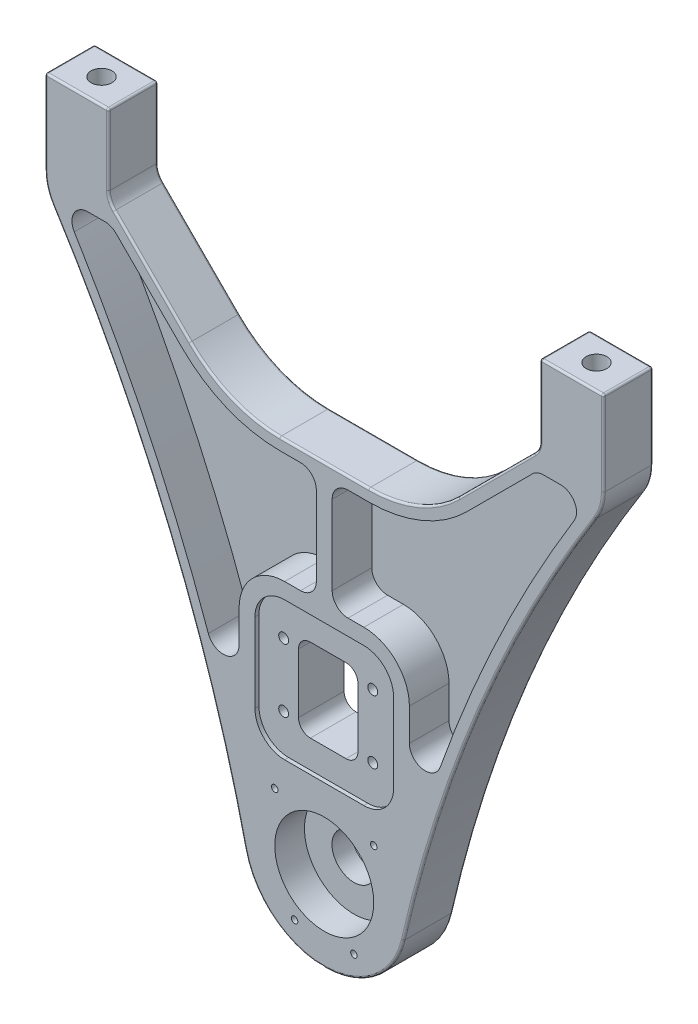
SolidWorks part; units mm, degrees
other "DetailItem2"
other "DetailItem3"
ref_plane "Front Plane" through (0, 0, 0) normal (0, 0, 1) x (1, 0, 0)
ref_plane "Top Plane" through (0, 0, 0) normal (0, 1, 0) x (1, 0, 0)
ref_plane "Right Plane" through (0, 0, 0) normal (1, 0, 0) x (0, 0, -1)
sketch "Sketch1" plane through (0, 0, 0) normal (0, 0, 1) x (1, 0, 0)
  line L0 (0, 0) -> (0, 280) construction
  line L1 (0, 280) -> (125, 280) construction
  line L2 (109, 280) -> (141, 280)
  line L3 (141, 280) -> (141, 237.3088)
  line L4 (109, 280) -> (109, 244.1421)
  line L5 (106.0711, 237.0711) -> (67.7452, 198.7452)
  line L6 (-22.4903, 180) -> (22.4903, 180)
  line L7 (0, 0) -> (0, -22.225) construction
  line L8 (-141, 280) -> (-141, 237.3088)
  line L9 (-109, 280) -> (-141, 280)
  line L10 (-109, 280) -> (-109, 244.1421)
  line L11 (-106.0711, 237.0711) -> (-67.7452, 198.7452)
  arc A0 (-39.9598, -9.1768) -> (39.9598, -9.1768) centre (0, 0) ccw
  circle A1 centre (0, 0) radius 22.5 construction
  arc A2 (137.1268, 223.9425) -> (39.9598, -9.1768) centre (770.9319, -177.0452) ccw
  arc A3 (67.7452, 198.7452) -> (22.4903, 180) centre (22.4903, 244) cw
  arc A4 (141, 237.3088) -> (137.1268, 223.9425) centre (116, 237.3088) cw
  arc A5 (109, 244.1421) -> (106.0711, 237.0711) centre (99, 244.1421) cw
  arc A6 (-137.1268, 223.9425) -> (-39.9598, -9.1768) centre (-770.9319, -177.0452) cw
  arc A7 (-141, 237.3088) -> (-137.1268, 223.9425) centre (-116, 237.3088) ccw
  arc A8 (-109, 244.1421) -> (-106.0711, 237.0711) centre (-99, 244.1421) ccw
  arc A9 (-67.7452, 198.7452) -> (-22.4903, 180) centre (-22.4903, 244) ccw
  circle A10 centre (0, 0) radius 10 construction
  point P24 (141, 230)
  point P27 (109, 240)
  point P35 (0, 180)
  dimension "D1" = 82
  dimension "D2" = 45
  dimension "D8" = 750
  dimension "D9" = 40
  dimension "D10" = 25
  dimension "D11" = 10
  dimension "D12" = 64
  dimension "D15" = 20
  dimension "D3" = 280
  dimension "D4" = 125
  dimension "D5" = 16
  dimension "D6" = 16
  dimension "D7" = 50
  dimension "D13" = 100
  dimension "D14" = 45
extrude "Boss-Extrude1" add sketch "Sketch1" along normal blind 25
sketch "Sketch2" plane through (0, 0, 25) normal (0, 0, 1) x (1, 0, 0)
  circle A0 centre (0, 0) radius 25
  dimension "D1" = 50
extrude "Cut-Extrude1" cut sketch "Sketch2" against normal blind 15
sketch "Sketch4" plane through (0, 0, 25) normal (0, 0, 1) x (1, 0, 0)
  line L9 (0, 0) -> (0, 180) construction
  line L10 (22.4903, 180) -> (-22.4903, 180) construction
  line L12 (-20, 40) -> (20, 40)
  line L13 (-35, 55) -> (-35, 95)
  line L14 (-20, 110) -> (20, 110)
  line L15 (35, 55) -> (35, 95)
  line L16 (-35, 40) -> (35, 110) construction
  line L17 (-35, 110) -> (35, 40) construction
  arc A7 (20, 40) -> (35, 55) centre (20, 55) ccw
  arc A8 (-20, 40) -> (-35, 55) centre (-20, 55) cw
  arc A9 (-35, 95) -> (-20, 110) centre (-20, 95) cw
  arc A10 (20, 110) -> (35, 95) centre (20, 95) cw
  point P8 (0, 75)
  dimension "D4" = 15
  dimension "D1" = 70
  dimension "D2" = 70
  dimension "D3" = 70
extrude "Cut-Extrude3" cut sketch "Sketch4" against normal blind 2
sketch "Sketch5" plane through (0, 0, 25) normal (0, 0, 1) x (1, 0, 0)
  line L0 (22.4903, 174) -> (12, 174)
  line L1 (141, 280) -> (109, 280) construction
  line L2 (106.0711, 237.0711) -> (67.7452, 198.7452) construction
  line L3 (22.4903, 180) -> (-22.4903, 180) construction
  line L4 (4, 166) -> (4, 126)
  line L5 (-43, 95) -> (-43, 78.6774)
  line L6 (-119.4268, 230) -> (-110.799, 230)
  line L7 (43, 95) -> (43, 78.6774)
  line L8 (0, 0) -> (0, 188.5352) construction
  line L9 (-105.1421, 227.6569) -> (-71.9878, 194.5025)
  line L10 (105.1421, 227.6569) -> (71.9878, 194.5025)
  line L11 (119.4268, 230) -> (110.799, 230)
  line L12 (20, 118) -> (-20, 118)
  line L13 (20, 118) -> (12, 118)
  line L14 (-22.4903, 174) -> (-12, 174)
  line L15 (-4, 166) -> (-4, 126)
  line L16 (-20, 118) -> (-12, 118)
  arc A0 (137.1268, 223.9425) -> (39.9598, -9.1768) centre (770.9319, -177.0452) ccw construction
  arc A1 (22.4903, 180) -> (67.7452, 198.7452) centre (22.4903, 244) ccw construction
  arc A2 (4, 126) -> (12, 118) centre (12, 126) ccw
  arc A3 (12, 174) -> (4, 166) centre (12, 166) ccw
  arc A4 (-43, 78.6774) -> (-58.5386, 75.9997) centre (-51, 78.6774) cw
  arc A5 (-58.5386, 75.9997) -> (-126.2488, 217.8215) centre (-770.9319, -177.0452) ccw
  arc A6 (-126.2488, 217.8215) -> (-119.4268, 230) centre (-119.4268, 222) cw
  arc A7 (43, 78.6774) -> (58.5386, 75.9997) centre (51, 78.6774) ccw
  arc A8 (-105.1421, 227.6569) -> (-110.799, 230) centre (-110.799, 222) ccw
  arc A9 (-71.9878, 194.5025) -> (-22.4903, 174) centre (-22.4903, 244) ccw
  arc A10 (-12, 174) -> (-4, 166) centre (-12, 166) cw
  arc A11 (-4, 126) -> (-12, 118) centre (-12, 126) cw
  arc A12 (-43, 95) -> (-20, 118) centre (-20, 95) cw
  arc A13 (71.9878, 194.5025) -> (22.4903, 174) centre (22.4903, 244) cw
  arc A14 (105.1421, 227.6569) -> (110.799, 230) centre (110.799, 222) cw
  arc A15 (126.2488, 217.8215) -> (119.4268, 230) centre (119.4268, 222) ccw
  arc A16 (58.5386, 75.9997) -> (126.2488, 217.8215) centre (770.9319, -177.0452) cw
  arc A17 (43, 95) -> (20, 118) centre (20, 95) ccw
  arc A18 (43, 95) -> (20, 118) centre (20, 95) ccw
  dimension "D4" = 6
  dimension "D5" = 6
  dimension "D6" = 8
  dimension "D8" = 8
  dimension "D1" = 6
  dimension "D3" = 6
  dimension "D9" = 8
  dimension "D10" = 8
  dimension "D7" = 4
  dimension "D2" = 50
extrude "Cut-Extrude4" cut sketch "Sketch5" against normal blind 20
fillet "Fillet1" radius 1 40 edges at (-140.0122, 230.3507, 25) (-141, 258.6544, 25) (-125, 280, 25) (-109, 262.0711, 25) (-108.2388, 240.3153, 25) (-86.9081, 217.9081, 25) (-46.9821, 184.8717, 25) (0, 180, 25) (46.9821, 184.8717, 25) (86.9081, 217.9081, 25) (108.2388, 240.3153, 25) (109, 262.0711, 25) (125, 280, 25) (141, 258.6544, 25) (140.0122, 230.3507, 25) (78.66, 111.5023, 25) (0, -41, 25) (-78.66, 111.5023, 25) (0, -41, 0) (78.66, 111.5023, 0) (140.0122, 230.3507, 0) (141, 258.6544, 0) (125, 280, 0) (109, 262.0711, 0) (108.2388, 240.3153, 0) (86.9081, 217.9081, 0) (46.9821, 184.8717, 0) (0, 180, 0) (-46.9821, 184.8717, 0) (-86.9081, 217.9081, 0) (-108.2388, 240.3153, 0) (-109, 262.0711, 0) (-125, 280, 0) (-141, 258.6544, 0) (-140.0122, 230.3507, 0) (-78.66, 111.5023, 0) (141, 280, 12.5) (109, 280, 12.5) (-109, 280, 12.5) (-141, 280, 12.5)
sketch "Sketch3" plane through (0, 0, 10) normal (0, 0, 1) x (1, 0, 0)
  circle A0 centre (0, 0) radius 11.1125
  dimension "D1" = 22.225
extrude "Cut-Extrude2" cut sketch "Sketch3" against normal blind 19.05
sketch "Sketch10" plane through (0, 0, 23) normal (0, 0, 1) x (1, 0, 0)
  line L4 (35, 75) -> (-35, 75) construction
  line L5 (35, 55) -> (35, 95) construction
  line L6 (-35, 95) -> (-35, 55) construction
  line L7 (0, 40) -> (0, 110) construction
  line L8 (-20, 40) -> (20, 40) construction
  line L9 (20, 110) -> (-20, 110) construction
  line L10 (0, 54) -> (0, 96) construction
  line L11 (15, 75) -> (-15, 75) construction
  line L12 (15, 60) -> (15, 90)
  line L13 (9, 96) -> (-9, 96)
  line L14 (-15, 90) -> (-15, 60)
  line L15 (-9, 54) -> (9, 54)
  arc A0 (-9, 54) -> (-15, 60) centre (-9, 60) cw
  arc A1 (-15, 90) -> (-9, 96) centre (-9, 90) cw
  arc A2 (9, 96) -> (15, 90) centre (9, 90) cw
  arc A3 (15, 60) -> (9, 54) centre (9, 60) cw
  dimension "D1" = 6
  dimension "D2" = 30
  dimension "D3" = 42
extrude "Cut-Extrude6" cut sketch "Sketch10" against normal through all
hole_wizard "M12x1.5 Tapped Hole1" positions "Sketch13" profile "Sketch14" tap size "M12x1.5" standard "ANSI Metric"
sketch "Sketch13" plane through (0, 280, 0) normal (0, 1, 0) x (1, 0, 0)
  line L0 (-125, -1) -> (-125, -24) construction
  line L1 (-110, -1) -> (-140, -1) construction
  line L2 (-140, -24) -> (-110, -24) construction
  line L3 (-125, -12.5) -> (-114.2971, -12.5) construction
  line L4 (0, 0) -> (0, 33.5417) construction
  point P3 (-125, -12.5)
  point P25 (125, -12.5)
cosmetic thread "Hole Thread7"
cosmetic thread "Hole Thread8"
sketch "Sketch14" plane through (-125, 280, 12.5) normal (1, 0, 0) x (0, 0, 1)
  line L0 (0, 0) -> (0, 34.6545)
  line L1 (0, 34.6545) -> (5.25, 31.5)
  line L2 (5.25, 31.5) -> (5.25, 0)
  line L5 (5.25, 0) -> (0, 0)
  line L10 (0, 34.6545) -> (-5.25, 31.5) construction
  line L11 (0, -6.35) -> (0, 107.95) construction
  dimension "Tap Drill Dia." = 10.5
  dimension "Tap Drill Depth" = 31.5
  dimension "Drill Angle" = 118
ref_plane "Plane1" through (30, 0, 0) normal (1, 0, 0) x (0, 0, -1)
sketch "Sketch15" plane through (30, 0, 0) normal (1, 0, 0) x (0, 0, -1)
  line L0 (-23, 75) -> (-41.1245, 75) construction
  line L1 (-23, 55) -> (-23, 95) construction
  line L3 (-25, 224.4771) -> (-25, -8.953) construction
  line L4 (-24.01, 100) -> (-24, 100)
  line L5 (-24, 223.9425) -> (-24, -9.1768) construction
  line L6 (-24.01, 50) -> (-24, 50)
  line L7 (-24, 50) -> (-24, 100)
  arc A0 (-24.01, 100) -> (-35.4885, 85.3051) centre (-39.0096, 99.886) cw
  arc A1 (-35.4885, 85.3051) -> (-35.4885, 64.6949) centre (-33, 75) ccw
  circle A2 centre (-33, 75) radius 5
  arc A3 (-24.01, 50) -> (-35.4885, 64.6949) centre (-39.0096, 50.114) ccw
  dimension "D1" = 10
  dimension "D2" = 8
  dimension "D3" = 15
  dimension "D4" = 25
  dimension "D5" = 0.01
extrude "Boss-Extrude2" [suppressed] add sketch "Sketch15" against normal up to vertex and the other way blind 0.0365
mirror "Mirror1" [suppressed] about plane through (0, 0, 0) normal (1, 0, 0)
hole_wizard "M4x0.7 Tapped Hole1" positions "Sketch18" profile "Sketch17" tap size "M4x0.7" standard "ANSI Metric"
sketch "Sketch18" plane through (0, 0, 25) normal (0, 0, 1) x (1, 0, 0)
  line L0 (0, 0) -> (0, 40) construction
  line L1 (-20, 40) -> (20, 40) construction
  line L2 (0, 0) -> (0, -40) construction
  line L3 (0, 0) -> (55.4877, 0) construction
  arc A0 (-38.9852, -8.953) -> (38.9852, -8.953) centre (0, 0) ccw construction
  point P17 (25, 25)
  point P21 (-25, 25)
  point P22 (15, -27.5)
  point P26 (-15, -27.5)
  dimension "D1" = 25
  dimension "D2" = 25
  dimension "D3" = 15
  dimension "D4" = 27.5
cosmetic thread "Hole Thread9"
cosmetic thread "Hole Thread10"
cosmetic thread "Hole Thread11"
cosmetic thread "Hole Thread12"
sketch "Sketch17" plane through (-15, -27.5, 25) normal (1, 0, 0) x (0, -1, 0)
  line L0 (0, 0) -> (0, 12.4914)
  line L1 (0, 12.4914) -> (1.65, 11.5)
  line L2 (1.65, 11.5) -> (1.65, 0)
  line L5 (1.65, 0) -> (0, 0)
  line L10 (0, 12.4914) -> (-1.65, 11.5) construction
  line L11 (0, -6.35) -> (0, 107.95) construction
  dimension "Tap Drill Dia." = 3.3
  dimension "Tap Drill Depth" = 11.5
  dimension "Drill Angle" = 118
sketch "Sketch21" [suppressed] plane through (0, 0, 23) normal (0, 0, 1) x (1, 0, 0)
  line L1 (15, 50) -> (30.0365, 50)
  line L2 (15, 50) -> (15, 100)
  line L3 (15, 100) -> (30.0365, 100)
  line L4 (30.0365, 50) -> (30.0365, 100)
  line L5 (-15, 50) -> (-30.0365, 50)
  line L6 (-15, 50) -> (-15, 100)
  line L7 (-15, 100) -> (-30.0365, 100)
  line L8 (-30.0365, 50) -> (-30.0365, 100)
hole_wizard "M6x1.0 Tapped Hole1" positions "Sketch22" profile "Sketch23" tap size "M6x1.0" standard "ANSI Metric"
sketch "Sketch22" plane through (0, 0, 23) normal (0, 0, 1) x (1, 0, 0)
  line L0 (0, 54) -> (0, 96) construction
  line L1 (-9, 54) -> (9, 54) construction
  line L2 (9, 96) -> (-9, 96) construction
  line L3 (-15, 75) -> (15, 75) construction
  line L4 (-15, 90) -> (-15, 60) construction
  line L5 (15, 60) -> (15, 90) construction
  point P0 (-22.5, 59)
  point P17 (-22.5, 91)
  point P20 (22.5, 91)
  point P21 (22.5, 59)
  dimension "D1" = 22.5
  dimension "D2" = 16
cosmetic thread "Hole Thread17"
cosmetic thread "Hole Thread18"
cosmetic thread "Hole Thread19"
cosmetic thread "Hole Thread20"
sketch "Sketch23" plane through (-22.5, 59, 23) normal (1, 0, 0) x (0, -1, 0)
  line L0 (0, 0) -> (0, 18.5022)
  line L1 (0, 18.5022) -> (2.5, 17)
  line L2 (2.5, 17) -> (2.5, 0)
  line L5 (2.5, 0) -> (0, 0)
  line L10 (0, 18.5022) -> (-2.5, 17) construction
  line L11 (0, -6.35) -> (0, 107.95) construction
  dimension "Tap Drill Dia." = 5
  dimension "Tap Drill Depth" = 17
  dimension "Drill Angle" = 118
sketch "Sketch24" plane through (0, 0, 25) normal (0, 0, 1) x (1, 0, 0)
  line L0 (0, -41) -> (0, -45.6187) construction
  line L2 (-0.1, -42.1947) -> (0.1, -42.1947)
  line L3 (-0.1, -42.1947) -> (-0.1, -40.99)
  line L4 (-0.1, -40.99) -> (0.1, -40.99)
  line L5 (0.1, -42.1947) -> (0.1, -40.99)
  arc A1 (-39.9598, -9.1768) -> (39.9598, -9.1768) centre (0, 0) ccw construction
  dimension "D1" = 0.1
  dimension "D2" = 0.1
  dimension "D3" = 0.01
extrude "Cut-Extrude7" cut sketch "Sketch24" against normal blind 3
